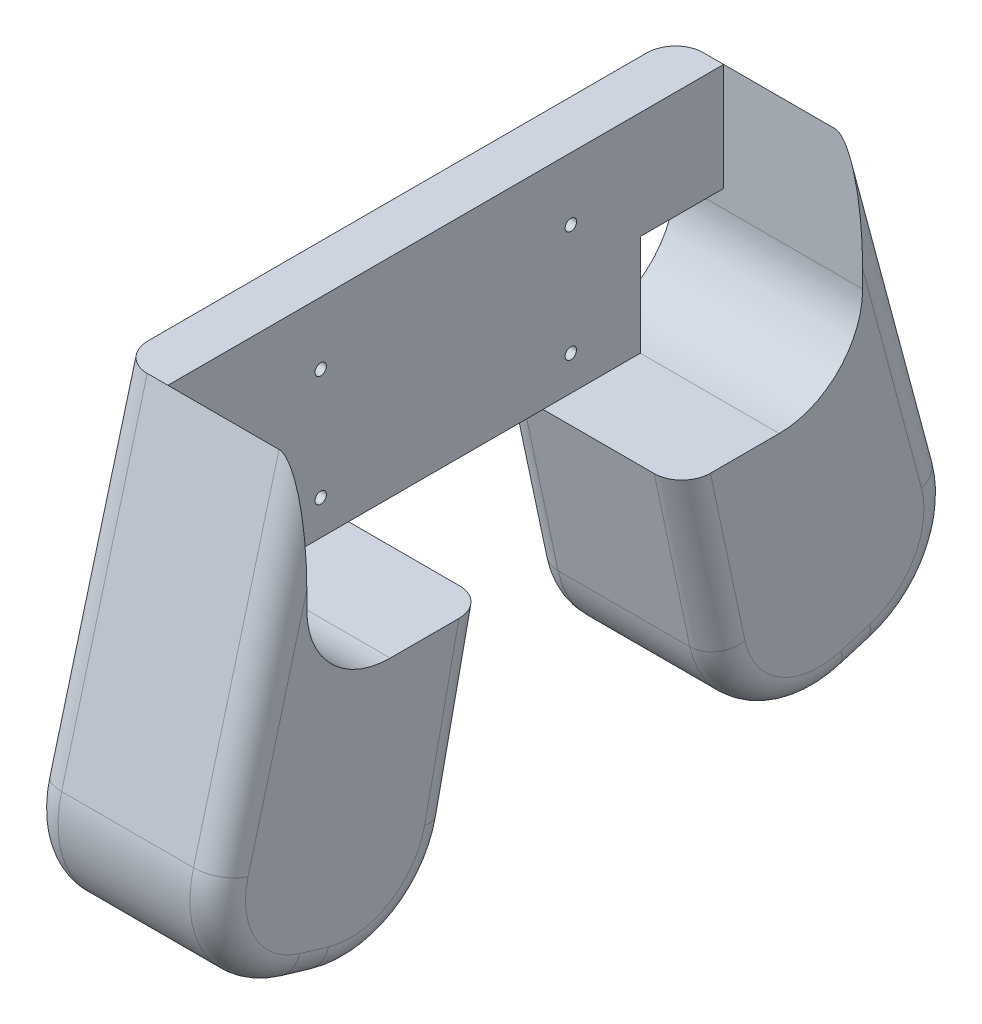
SolidWorks part; units mm, degrees
ref_plane "Front Plane" through (0, 0, 0) normal (0, 0, 1) x (1, 0, 0)
ref_plane "Top Plane" through (0, 0, 0) normal (0, 1, 0) x (1, 0, 0)
ref_plane "Right Plane" through (0, 0, 0) normal (1, 0, 0) x (0, 0, -1)
sketch "Sketch2" plane through (0, 0, 0) normal (1, 0, 0) x (0, 0, -1)
  line L0 (-70, 75) -> (70, 75) construction
  line L1 (100, 0) -> (-100, 0) construction
  line L2 (0, 75) -> (0, -75) construction
  line L3 (-100, 45) -> (-100, -45) construction
  line L4 (-70, -75) -> (70, -75) construction
  line L5 (100, 45) -> (100, -45) construction
  line L6 (-60.582, 0) -> (60.582, 0) construction
  line L7 (-70, -75) -> (-70, -65) construction
  line L8 (70, -75) -> (70, -65) construction
  line L9 (70, -65) -> (0, -65) construction
  line L10 (35, -65) -> (35, -75) construction
  line L11 (100, 0) -> (130.7929, -114.9205)
  line L12 (105.3865, -160.3667) -> (95.0235, -163.4532)
  line L13 (47.8454, -135.4331) -> (35, -75)
  line L14 (-70, -65) -> (0, -65) construction
  line L15 (-35, -65) -> (-35, -75) construction
  line L16 (-35, -75) -> (-47.8454, -135.4331)
  line L17 (-95.0235, -163.4532) -> (-105.3865, -160.3667)
  line L18 (-130.7929, -114.9205) -> (-100, 0)
  line L19 (-100, 0) -> (-35, 0)
  line L22 (35, 0) -> (100, 0)
  line L24 (-35, 0) -> (35, 0)
  line L26 (-35, -75) -> (35, -75)
  arc A0 (70, 75) -> (100, 45) centre (70, 45) cw construction
  arc A1 (-70, 75) -> (-100, 45) centre (-70, 45) ccw construction
  arc A2 (-100, -45) -> (-70, -75) centre (-70, -45) ccw construction
  arc A3 (70, -75) -> (100, -45) centre (70, -45) ccw construction
  arc A4 (130.7929, -114.9205) -> (105.3865, -160.3667) centre (94.7288, -124.5839) cw
  arc A5 (95.0235, -163.4532) -> (47.8454, -135.4331) centre (84.3658, -127.6704) cw
  arc A6 (-105.3865, -160.3667) -> (-130.7929, -114.9205) centre (-94.7288, -124.5839) cw
  arc A7 (-47.8454, -135.4331) -> (-95.0235, -163.4532) centre (-84.3658, -127.6704) cw
  point P0 (0, 0)
  point P17 (0, 0)
  point P22 (0, 0)
  point P23 (35, -65)
  point P33 (140.1924, -150)
  point P36 (56.2557, -175)
  dimension "D3" = 30
  dimension "D8" = 37.3363
  dimension "D12" = 150
  dimension "D2" = 200
  dimension "D4" = 102
  dimension "D5" = 165
  dimension "D6" = 100
  dimension "D7" = 150
  dimension "D9" = 10
  dimension "D10" = 102
  dimension "D11" = 165
extrude "Boss-Extrude1" add sketch "Sketch2" along normal blind 10 and the other way blind 7.4377
sketch "Sketch3" plane through (10, 0, 0) normal (1, 0, 0) x (0, 0, -1)
  line L0 (-70, 75) -> (70, 75) construction
  line L1 (100, 0) -> (-100, 0) construction
  line L2 (0, 75) -> (0, -75) construction
  line L3 (-100, 45) -> (-100, -45) construction
  line L4 (-70, -75) -> (70, -75) construction
  line L5 (100, 45) -> (100, -45) construction
  line L6 (142.8275, 0) -> (-142.8275, 0) construction
  line L7 (-70, -75) -> (-70, -65) construction
  line L8 (70, -75) -> (70, -65) construction
  line L9 (70, -65) -> (0, -65) construction
  line L10 (35, -65) -> (35, -75) construction
  line L11 (100, 0) -> (130.7929, -114.9205)
  line L12 (105.3865, -160.3667) -> (95.0235, -163.4532)
  line L13 (47.8454, -135.4331) -> (35, -75)
  line L14 (-70, -65) -> (0, -65) construction
  line L15 (-35, -65) -> (-35, -75) construction
  line L16 (-35, -75) -> (-47.8454, -135.4331)
  line L17 (-95.0235, -163.4532) -> (-105.3865, -160.3667)
  line L18 (-130.7929, -114.9205) -> (-100, 0)
  line L19 (-100, -45) -> (-100, 0)
  line L20 (-70, -75) -> (-35, -75)
  line L21 (35, -75) -> (70, -75)
  line L22 (100, -45) -> (100, 0)
  arc A0 (70, 75) -> (100, 45) centre (70, 45) cw construction
  arc A1 (-70, 75) -> (-100, 45) centre (-70, 45) ccw construction
  arc A2 (-100, -45) -> (-70, -75) centre (-70, -45) ccw
  arc A3 (70, -75) -> (100, -45) centre (70, -45) ccw
  arc A4 (130.7929, -114.9205) -> (105.3865, -160.3667) centre (94.7288, -124.5839) cw
  arc A5 (95.0235, -163.4532) -> (47.8454, -135.4331) centre (84.3658, -127.6704) cw
  arc A6 (-105.3865, -160.3667) -> (-130.7929, -114.9205) centre (-94.7288, -124.5839) cw
  arc A7 (-47.8454, -135.4331) -> (-95.0235, -163.4532) centre (-84.3658, -127.6704) cw
  point P0 (0, 0)
  point P17 (0, 0)
  point P22 (0, 0)
  point P23 (35, -65)
  dimension "D1" = 30
  dimension "D4" = 37.3363
  dimension "D2" = 102
  dimension "D3" = 165
  dimension "D5" = 10
  dimension "D6" = 102
  dimension "D7" = 165
  dimension "D8" = 200
  dimension "D9" = 150
extrude "Boss-Extrude2" add sketch "Sketch3" along normal blind 50
fillet "Fillet7" radius 10 5 edges at (60, -105.2165, 41.4227) (60, -159.7717, 65.3001) (60, -161.91, 100.205) (60, -142.8028, 127.3182) (60, -57.4603, 115.3964)
fillet "Fillet9" radius 10 5 edges at (60, -57.4603, -115.3964) (60, -159.7717, -65.3001) (60, -142.8028, -127.3182) (60, -161.91, -100.205) (60, -105.2165, -41.4227)
fillet "Fillet10" radius 10 10 edges at (-7.4377, -57.4603, -115.3964) (-7.4377, -142.8028, -127.3182) (-7.4377, -161.91, -100.205) (-7.4377, -159.7717, -65.3001) (-7.4377, -105.2165, -41.4227) (-7.4377, -57.4603, 115.3964) (-7.4377, -142.8028, 127.3182) (-7.4377, -161.91, 100.205) (-7.4377, -159.7717, 65.3001) (-7.4377, -105.2165, 41.4227)
sketch "Sketch5" plane through (10, 0, 0) normal (1, 0, 0) x (0, 0, -1)
  line L0 (-90, -62.5) -> (90, -62.5) construction
  line L1 (-35, -75) -> (35, -75) construction
  line L2 (-90, -62.5) -> (0, -62.5) construction
  line L3 (0, -62.5) -> (-90, -62.5) construction
  line L4 (0, -62.5) -> (90, -62.5) construction
  line L5 (0, -62.5) -> (-90, -62.5) construction
  line L6 (0, -62.5) -> (0, -53.5) construction
  line L7 (0, -53.5) -> (-90, -53.5) construction
  line L8 (-45, -53.5) -> (-45, -62.5) construction
  line L10 (-45, -62.5) -> (45, -62.5) construction
  line L11 (-45, -62.5) -> (-45, -22.5) construction
  line L12 (-45, -22.5) -> (45, -22.5) construction
  line L13 (45, -62.5) -> (45, -22.5) construction
  circle A1 centre (45, -62.5) radius 2.05
  circle A2 centre (-45, -62.5) radius 2.05
  circle A3 centre (-45, -22.5) radius 2.05
  circle A4 centre (45, -22.5) radius 2.05
  point P0 (45, -62.5)
  point P3 (0, -62.5)
  point P11 (-45, -53.5)
  point P13 (-74.5386, -62.5)
  dimension "D3" = 4.1
  dimension "D1" = 180
  dimension "D2" = 12.5
  dimension "D4" = 9
  dimension "D5" = 90
  dimension "D6" = 40
  dimension "D7" = 90
extrude "Cut-Extrude1" cut sketch "Sketch5" against normal blind 30 and the other way blind 30
sketch "Sketch7" plane through (10, 0, 0) normal (1, 0, 0) x (0, 0, -1)
  line L0 (-100, -45) -> (-100, 0) construction
  line L1 (-100, -38.637) -> (-70, -38.637)
  line L2 (-100, -38.637) -> (-100, -45.1723) construction
  line L3 (-70.1723, -75) -> (-70, -75) construction
  line L4 (-70, -38.637) -> (-70, -75)
  line L5 (-100, -38.637) -> (-121.1336, -117.5087) construction
  line L6 (100, -45.1723) -> (100, -38.637)
  line L7 (70, -75) -> (70.1723, -75) construction
  line L8 (70, -75) -> (70, -38.637)
  line L9 (70, -38.637) -> (100, -38.637)
  line L10 (100, -45.1723) -> (100, -38.637) construction
  line L11 (-100, -45.1723) -> (-100, -38.637)
  line L12 (-70.1723, -75) -> (-70, -75)
  line L13 (70, -75) -> (70.1723, -75)
  arc A0 (-100, -45.1723) -> (-70.1723, -75) centre (-70.1723, -45.1723) ccw
  arc A1 (70.1723, -75) -> (100, -45.1723) centre (70.1723, -45.1723) ccw
  line M17 (-100, 0) -> (-100, -45)
  arc M18 (-100, -45) -> (-70, -75) centre (-70, -45) ccw
  arc M22 (70, -75) -> (100, -45) centre (70, -45) ccw
  line M23 (100, -45) -> (100, 0)
  dimension "D1" = 29.8277
extrude "Cut-Extrude2" cut sketch "Sketch7" against normal blind 30 contours L9 L8 M22 M23 | L4 L1 M17 M18 | L12 L4 L1 L11 A0 region at (10, -54.3486, 83.2146) region at (10, -54.3486, -83.2146)
